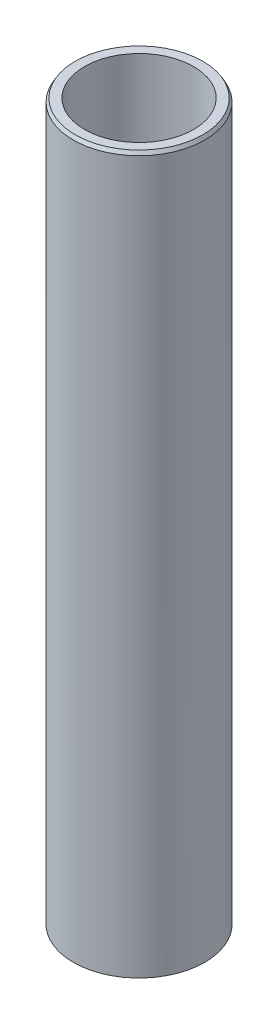
SolidWorks part; units mm, degrees
ref_plane "Front Plane" through (0, 0, 0) normal (0, 0, 1) x (1, 0, 0)
ref_plane "Top Plane" through (0, 0, 0) normal (0, 1, 0) x (1, 0, 0)
ref_plane "Right Plane" through (0, 0, 0) normal (1, 0, 0) x (0, 0, -1)
sketch "Sketch1" plane through (0, 0, 0) normal (0, 1, 0) x (1, 0, 0)
  circle A0 centre (0, 0) radius 55
  dimension "SHAFT_OD" = 110
extrude "Boss-Extrude1" add sketch "Sketch1" along normal blind 600
sketch "Sketch2" plane through (0, 0, 0) normal (0, 1, 0) x (1, 0, 0)
  circle A0 centre (0, 0) radius 45.613
  dimension "BORE_D" = 91.226
extrude "Cut-Extrude1" cut sketch "Sketch2" along normal through all
chamfer "Chamfer1" distance 2.9219 angle 30 2 edges at (0, 600, 55) (0, 0, 55) first distance on face at (0, 600, 55) first distance on face at (0, 0, 45.613)
